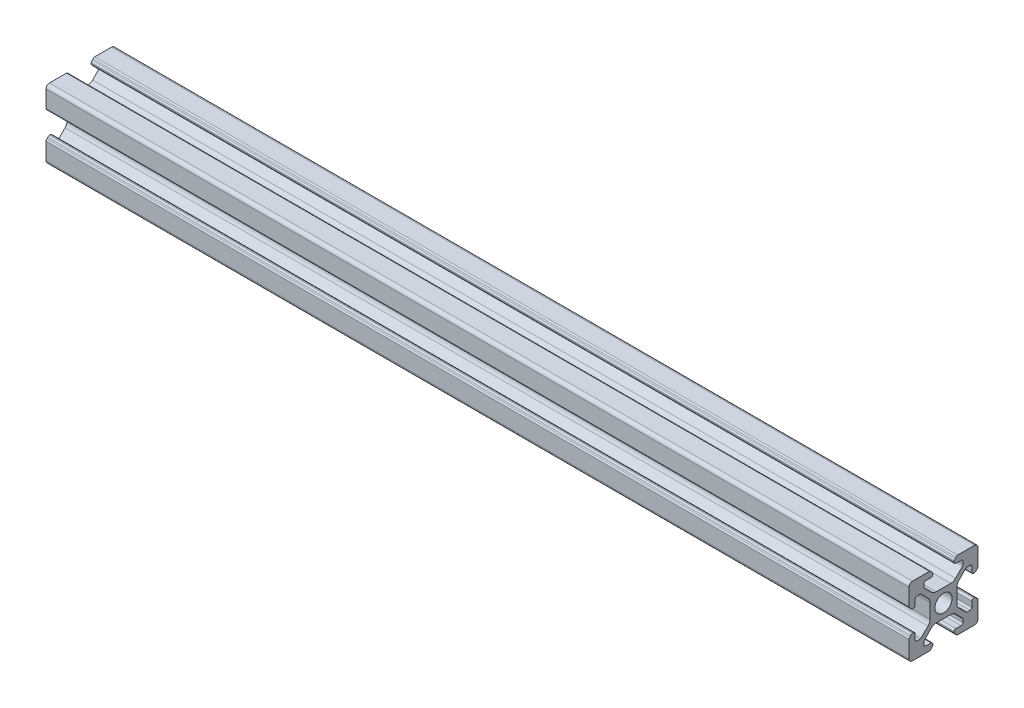
SolidWorks part; units mm, degrees
material "6061 Alloy"
ref_plane "Front Plane" through (0, 0, 0) normal (0, 0, 1) x (1, 0, 0)
ref_plane "Top Plane" through (0, 0, 0) normal (0, 1, 0) x (1, 0, 0)
ref_plane "Right Plane" through (0, 0, 0) normal (1, 0, 0) x (0, 0, -1)
sketch "Sketch1" plane through (0, 0, 0) normal (1, 0, 0) x (0, 0, -1)
  line L0 (10, 10) -> (-10, -10) construction
  line L1 (-10, 10) -> (10, 10)
  line L2 (-10, 10) -> (-10, -10)
  line L3 (-10, -10) -> (10, -10)
  line L4 (10, 10) -> (10, -10)
  dimension "D1" = 20
extrude "Boss-Extrude1" add sketch "Sketch1" along normal blind 250
fillet "Fillet1" radius 1 4 edges at (125, -10, -10) (125, -10, 10) (125, 10, -10) (125, 10, 10)
sketch "Sketch3" plane through (0, 0, 0) normal (-1, 0, 0) x (0, 0, 1)
  line L0 (-3.6, 10) -> (3.6, 10)
  line L1 (-9, 10) -> (9, 10) construction
  line L2 (3.6, 10) -> (3.6, 9.5)
  line L3 (3.6, 9.5) -> (3.1, 9.5)
  line L4 (3.1, 9.5) -> (3.1, 8.2)
  line L5 (3.1, 8.2) -> (5.63, 8.2)
  line L6 (5.63, 8.2) -> (5.63, 6.6199)
  line L7 (5.63, 6.6199) -> (2.9101, 3.9)
  line L8 (2.9101, 3.9) -> (-2.9101, 3.9)
  line L9 (-2.9101, 3.9) -> (-5.63, 6.6199)
  line L10 (-5.63, 6.6199) -> (-5.63, 8.2)
  line L11 (-5.63, 8.2) -> (-3.1, 8.2)
  line L12 (-3.1, 8.2) -> (-3.1, 9.5)
  line L13 (-3.1, 9.5) -> (-3.6, 9.5)
  line L14 (-3.6, 9.5) -> (-3.6, 10)
  line L15 (0, 10) -> (0, 3.9) construction
  line L16 (10, 3.6) -> (10, -3.6)
  line L17 (10, -3.6) -> (9.5, -3.6)
  line L18 (9.5, -3.6) -> (9.5, -3.1)
  line L19 (9.5, -3.1) -> (8.2, -3.1)
  line L20 (8.2, -3.1) -> (8.2, -5.63)
  line L21 (8.2, -5.63) -> (6.6199, -5.63)
  line L22 (6.6199, -5.63) -> (3.9, -2.9101)
  line L23 (3.9, -2.9101) -> (3.9, 2.9101)
  line L24 (3.9, 2.9101) -> (6.6199, 5.63)
  line L25 (6.6199, 5.63) -> (8.2, 5.63)
  line L26 (8.2, 5.63) -> (8.2, 3.1)
  line L27 (8.2, 3.1) -> (9.5, 3.1)
  line L28 (9.5, 3.1) -> (9.5, 3.6)
  line L29 (9.5, 3.6) -> (10, 3.6)
  line L30 (10, 0) -> (3.9, 0) construction
  line L31 (3.6, -10) -> (-3.6, -10)
  line L32 (-3.6, -10) -> (-3.6, -9.5)
  line L33 (-3.6, -9.5) -> (-3.1, -9.5)
  line L34 (-3.1, -9.5) -> (-3.1, -8.2)
  line L35 (-3.1, -8.2) -> (-5.63, -8.2)
  line L36 (-5.63, -8.2) -> (-5.63, -6.6199)
  line L37 (-5.63, -6.6199) -> (-2.9101, -3.9)
  line L38 (-2.9101, -3.9) -> (2.9101, -3.9)
  line L39 (2.9101, -3.9) -> (5.63, -6.6199)
  line L40 (5.63, -6.6199) -> (5.63, -8.2)
  line L41 (5.63, -8.2) -> (3.1, -8.2)
  line L42 (3.1, -8.2) -> (3.1, -9.5)
  line L43 (3.1, -9.5) -> (3.6, -9.5)
  line L44 (3.6, -9.5) -> (3.6, -10)
  line L45 (0, -10) -> (0, -3.9) construction
  line L46 (-10, -3.6) -> (-10, 3.6)
  line L47 (-10, 3.6) -> (-9.5, 3.6)
  line L48 (-9.5, 3.6) -> (-9.5, 3.1)
  line L49 (-9.5, 3.1) -> (-8.2, 3.1)
  line L50 (-8.2, 3.1) -> (-8.2, 5.63)
  line L51 (-8.2, 5.63) -> (-6.6199, 5.63)
  line L52 (-6.6199, 5.63) -> (-3.9, 2.9101)
  line L53 (-3.9, 2.9101) -> (-3.9, -2.9101)
  line L54 (-3.9, -2.9101) -> (-6.6199, -5.63)
  line L55 (-6.6199, -5.63) -> (-8.2, -5.63)
  line L56 (-8.2, -5.63) -> (-8.2, -3.1)
  line L57 (-8.2, -3.1) -> (-9.5, -3.1)
  line L58 (-9.5, -3.1) -> (-9.5, -3.6)
  line L59 (-9.5, -3.6) -> (-10, -3.6)
  line L60 (-10, 0) -> (-3.9, 0) construction
  line L61 (10, 9) -> (10, -9) construction
  line L62 (-10, -9) -> (-10, 9) construction
  point P4 (0, 10)
  point P17 (0, 0)
  point P26 (10, 0)
  point P43 (0, -10)
  point P60 (-10, 0)
  point P75 (0, 0)
  dimension "D1" = 135
  dimension "D2" = 6.2
  dimension "D3" = 7.2
  dimension "D4" = 6.1
  dimension "D5" = 11.26
  dimension "D6" = 0.5
  dimension "D8" = 1.4
  dimension "D9" = 1.8
  dimension "D7" = 4
extrude "Cut-Extrude1" cut sketch "Sketch3" against normal through all
hole_wizard "Ø5.0 (5) Diameter Hole1" positions "Sketch4" profile "Sketch5" hole size "Ø5.0" standard "ANSI Metric" end condition through all
sketch "Sketch4" plane through (0, 0, 0) normal (-1, 0, 0) x (0, 0, 1)
  point P0 (0, 0)
sketch "Sketch5" plane through (0, 0, 0) normal (0, 1, 0) x (0, 0, 1)
  line L0 (0, 0) -> (0, 250)
  line L1 (0, 250) -> (2.5, 250)
  line L2 (2.5, 250) -> (2.5, 0)
  line L5 (2.5, 0) -> (0, 0)
  line L11 (0, -6.35) -> (0, 107.95) construction
  dimension "Thru Hole Dia." = 5
  dimension "Thru Hole Depth" = 250
fillet "Fillet2" radius 2 8 edges at (125, -3.9, -2.9101) (125, -3.9, 2.9101) (125, -2.9101, 3.9) (125, 2.9101, 3.9) (125, 3.9, 2.9101) (125, 3.9, -2.9101) (125, 2.9101, -3.9) (125, -2.9101, -3.9)
fillet "Fillet3" radius 0.5 20 edges at (125, 3.6, -10) (125, 3.1, -9.5) (125, 3.1, -8.2) (125, 5.63, -8.2) (125, 5.63, -6.6199) (125, 3.6, 10) (125, 3.1, 9.5) (125, 3.1, 8.2) (125, 5.63, 8.2) (125, 5.63, 6.6199) (125, 6.6199, 5.63) (125, 8.2, 5.63) (125, 8.2, 3.1) (125, 9.5, 3.1) (125, 10, 3.6) (125, 9.5, -3.1) (125, 10, -3.6) (125, 8.2, -3.1) (125, 8.2, -5.63) (125, 6.6199, -5.63)
fillet "Fillet4" radius 0.5 20 edges at (125, -3.6, 10) (125, -3.1, 9.5) (125, -3.1, 8.2) (125, -5.63, 8.2) (125, -5.63, 6.6199) (125, -6.6199, 5.63) (125, -8.2, 5.63) (125, -8.2, 3.1) (125, -10, 3.6) (125, -9.5, 3.1) (125, -10, -3.6) (125, -9.5, -3.1) (125, -8.2, -3.1) (125, -8.2, -5.63) (125, -6.6199, -5.63) (125, -5.63, -6.6199) (125, -5.63, -8.2) (125, -3.1, -8.2) (125, -3.1, -9.5) (125, -3.6, -10)
fillet "Fillet5" radius 0.5 8 edges at (125, 3.6, -9.5) (125, -3.6, -9.5) (125, -9.5, -3.6) (125, -9.5, 3.6) (125, -3.6, 9.5) (125, 3.6, 9.5) (125, 9.5, 3.6) (125, 9.5, -3.6)
